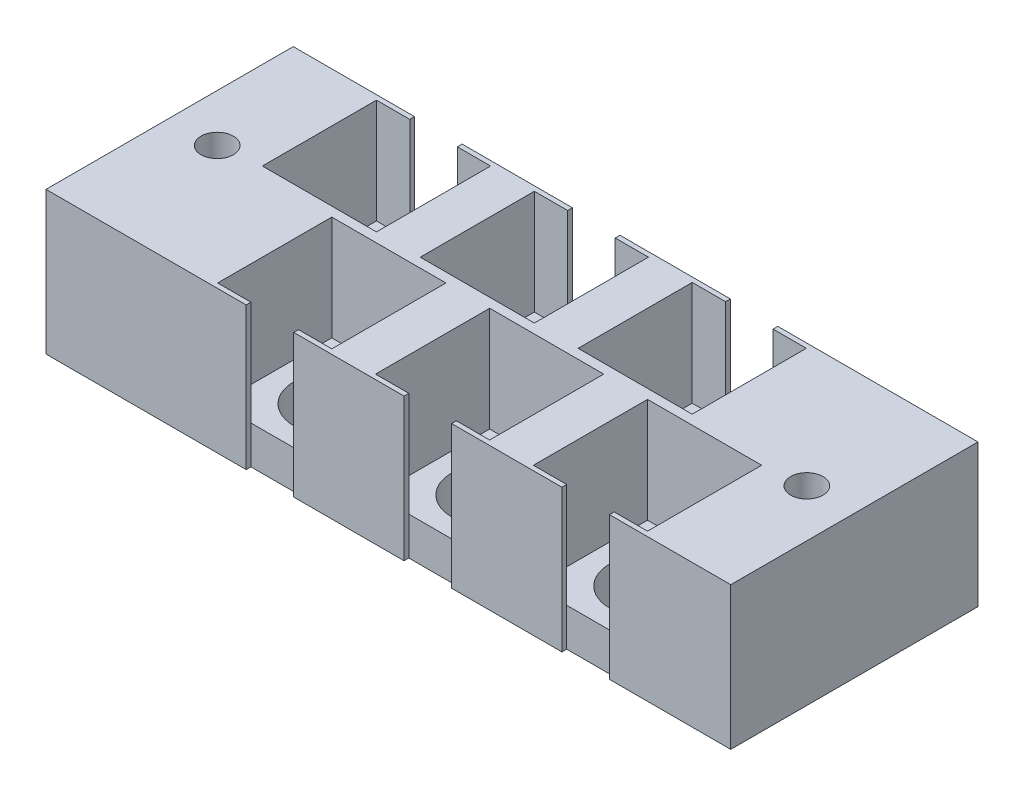
SolidWorks part; units mm, degrees
ref_plane "Front Plane" through (0, 0, 0) normal (0, 0, 1) x (1, 0, 0)
ref_plane "Top Plane" through (0, 0, 0) normal (0, 1, 0) x (1, 0, 0)
ref_plane "Right Plane" through (0, 0, 0) normal (1, 0, 0) x (0, 0, -1)
sketch "Sketch1" plane through (0, 0, 0) normal (0, 1, 0) x (1, 0, 0)
  line L0 (5.3864, -4.1649) -> (1.7864, -4.1649)
  line L1 (18.3864, -4.1649) -> (21.9864, -4.1649)
  line L2 (30.2864, -30.1649) -> (26.6864, -30.1649)
  line L3 (13.6864, -30.1649) -> (10.0864, -30.1649)
  line L4 (43.2864, -30.1649) -> (52.0364, -30.1649)
  line L5 (52.0364, -30.1649) -> (52.0364, -4.1649)
  line L6 (52.0364, -4.1649) -> (34.9864, -4.1649)
  line L7 (-11.2136, -4.1649) -> (-19.9636, -4.1649)
  line L8 (-19.9636, -4.1649) -> (-19.9636, -30.1649)
  line L9 (-19.9636, -30.1649) -> (-2.9136, -30.1649)
  line L10 (-14.9636, -4.1649) -> (-14.9636, -30.1649) construction
  line L11 (47.0364, -4.1649) -> (47.0364, -30.1649) construction
  circle A0 centre (-14.9636, -17.1649) radius 1.7
  circle A1 centre (47.0364, -17.1649) radius 1.7
  line B0 (34.9864, -17.1649) -> (34.9864, -4.1649)
  line B1 (10.0864, -30.1649) -> (6.0864, -30.1649)
  line B2 (-2.4136, -29.6649) -> (9.5864, -29.6649)
  line B3 (10.0864, -30.1649) -> (10.0864, -17.1649)
  line B4 (26.6864, -30.1649) -> (26.6864, -17.1649)
  line B5 (43.2864, -30.1649) -> (43.2864, -17.1649)
  line B6 (-2.9136, -17.1649) -> (-2.9136, -30.1649)
  line B7 (9.5864, -29.6649) -> (9.5864, -17.6649)
  line B8 (30.2864, -17.1649) -> (30.2864, -30.1649)
  line B9 (21.9864, -4.1649) -> (21.9864, -17.1649)
  line B10 (34.4864, -16.6649) -> (34.4864, -4.6649)
  line B11 (17.8864, -16.6649) -> (17.8864, -4.6649)
  line B12 (1.7864, -17.1649) -> (1.7864, -4.1649)
  line B13 (42.7864, -29.6649) -> (42.7864, -17.6649)
  line B14 (14.1864, -29.6649) -> (26.1864, -29.6649)
  line B15 (30.7864, -17.6649) -> (30.7864, -29.6649)
  line B16 (30.7864, -17.6649) -> (42.7864, -29.6649) construction
  line B17 (14.1864, -17.6649) -> (26.1864, -29.6649) construction
  line B18 (-2.4136, -17.6649) -> (9.5864, -29.6649) construction
  line B19 (43.2864, -17.1649) -> (30.2864, -17.1649)
  line B20 (1.2864, -16.6649) -> (1.2864, -4.6649)
  line B21 (14.1864, -17.6649) -> (14.1864, -29.6649)
  line B22 (26.6864, -30.1649) -> (22.6864, -30.1649)
  line B23 (30.2864, -30.1649) -> (34.2864, -30.1649)
  line B24 (43.2864, -30.1649) -> (39.2864, -30.1649)
  line B25 (-10.7136, -10.6649) -> (1.2864, -10.6649) construction
  line B26 (5.8864, -10.6649) -> (17.8864, -10.6649) construction
  line B27 (22.4864, -10.6649) -> (34.4864, -10.6649) construction
  line B28 (-2.4136, -23.6649) -> (9.5864, -23.6649) construction
  line B29 (14.1864, -23.6649) -> (26.1864, -23.6649) construction
  line B30 (30.7864, -23.6649) -> (42.7864, -23.6649) construction
  line B31 (-27.9152, -23.6649) -> (50.7342, -23.6649) construction
  line B32 (21.9864, -17.1649) -> (34.9864, -17.1649)
  line B33 (-27.9152, -10.6649) -> (50.7342, -10.6649) construction
  line B34 (28.4864, -16.6649) -> (28.4864, -4.6649) construction
  line B35 (36.7864, -17.6649) -> (36.7864, -29.6649) construction
  line B36 (20.1864, -17.6649) -> (20.1864, -29.6649) construction
  line B37 (11.8864, -16.6649) -> (11.8864, -4.6649) construction
  line B38 (3.5864, -17.6649) -> (3.5864, -29.6649) construction
  line B39 (-4.7136, -16.6649) -> (-4.7136, -4.6649) construction
  line B40 (22.4864, -4.6649) -> (22.4864, -16.6649)
  line B41 (22.4864, -16.6649) -> (34.4864, -16.6649)
  line B42 (34.4864, -4.6649) -> (22.4864, -4.6649)
  line B43 (34.4864, -16.6649) -> (22.4864, -4.6649) construction
  line B44 (34.4864, -4.6649) -> (22.4864, -16.6649) construction
  line B45 (34.9864, -4.1649) -> (30.9864, -4.1649)
  line B46 (21.9864, -4.1649) -> (25.9864, -4.1649)
  line B47 (30.9864, -4.1649) -> (30.9864, -4.6649)
  line B48 (25.9864, -4.1649) -> (25.9864, -4.6649)
  circle B49 centre (28.4864, -10.6649) radius 4
  line B50 (-2.4136, -17.6649) -> (-2.4136, -29.6649)
  line B51 (9.5864, -17.6649) -> (-2.4136, -17.6649)
  line B52 (-2.4136, -29.6649) -> (9.5864, -17.6649) construction
  line B53 (10.0864, -17.1649) -> (-2.9136, -17.1649)
  line B54 (-2.9136, -30.1649) -> (1.0864, -30.1649)
  line B55 (1.0864, -30.1649) -> (1.0864, -29.6649)
  line B56 (6.0864, -30.1649) -> (6.0864, -29.6649)
  circle B57 centre (3.5864, -23.6649) radius 4
  line B58 (26.1864, -29.6649) -> (26.1864, -17.6649)
  line B59 (26.1864, -17.6649) -> (14.1864, -17.6649)
  line B60 (14.1864, -29.6649) -> (26.1864, -17.6649) construction
  line B61 (26.6864, -17.1649) -> (13.6864, -17.1649)
  line B62 (13.6864, -17.1649) -> (13.6864, -30.1649)
  line B63 (13.6864, -30.1649) -> (17.6864, -30.1649)
  line B64 (17.6864, -30.1649) -> (17.6864, -29.6649)
  line B65 (22.6864, -30.1649) -> (22.6864, -29.6649)
  circle B66 centre (20.1864, -23.6649) radius 4
  line B67 (42.7864, -17.6649) -> (30.7864, -17.6649)
  line B68 (30.7864, -29.6649) -> (42.7864, -29.6649)
  line B69 (30.7864, -29.6649) -> (42.7864, -17.6649) construction
  line B70 (34.2864, -30.1649) -> (34.2864, -29.6649)
  line B71 (39.2864, -30.1649) -> (39.2864, -29.6649)
  circle B72 centre (36.7864, -23.6649) radius 4
  line B73 (5.8864, -4.6649) -> (5.8864, -16.6649)
  line B74 (5.8864, -16.6649) -> (17.8864, -16.6649)
  line B75 (17.8864, -4.6649) -> (5.8864, -4.6649)
  line B76 (17.8864, -16.6649) -> (5.8864, -4.6649) construction
  line B77 (17.8864, -4.6649) -> (5.8864, -16.6649) construction
  line B78 (5.3864, -17.1649) -> (18.3864, -17.1649)
  line B79 (18.3864, -17.1649) -> (18.3864, -4.1649)
  line B80 (5.3864, -4.1649) -> (5.3864, -17.1649)
  line B81 (18.3864, -4.1649) -> (14.3864, -4.1649)
  line B82 (5.3864, -4.1649) -> (9.3864, -4.1649)
  line B83 (14.3864, -4.1649) -> (14.3864, -4.6649)
  line B84 (9.3864, -4.1649) -> (9.3864, -4.6649)
  circle B85 centre (11.8864, -10.6649) radius 4
  line B86 (-10.7136, -4.6649) -> (-10.7136, -16.6649)
  line B87 (-10.7136, -16.6649) -> (1.2864, -16.6649)
  line B88 (1.2864, -4.6649) -> (-10.7136, -4.6649)
  line B89 (1.2864, -16.6649) -> (-10.7136, -4.6649) construction
  line B90 (1.2864, -4.6649) -> (-10.7136, -16.6649) construction
  line B91 (-11.2136, -17.1649) -> (1.7864, -17.1649)
  line B92 (-11.2136, -4.1649) -> (-11.2136, -17.1649)
  line B93 (1.7864, -4.1649) -> (-2.2136, -4.1649)
  line B94 (-11.2136, -4.1649) -> (-7.2136, -4.1649)
  line B95 (-2.2136, -4.1649) -> (-2.2136, -4.6649)
  line B96 (-7.2136, -4.1649) -> (-7.2136, -4.6649)
  circle B97 centre (-4.7136, -10.6649) radius 4
  dimension "D1" = 8.75
  dimension "D2" = 8.75
  dimension "D3" = 5
  dimension "D4" = 5
sketch_block_instance "Block1-5"
sketch_block "Block1" parameters "D3"=6, "D1"=12, "D2"=12, "D4"=12, "D5"=78.6494, "D6"=78.6494, "D7"=78.6494, "D8"=10.3235, "D9"=14.0261, "D10"=17.7654, "D11"=23.7534, "D12"=22.7743, "D13"=54.5
sketch_block_instance "Block2-2"
sketch_block "Block2" parameters "D1"=12
sketch_block_instance "Block2-3"
sketch_block_instance "Block2-4"
sketch_block_instance "Block2-5"
sketch_block_instance "Block2-6"
sketch_block_instance "Block2-7"
sketch_block_instance "Block3-1"
sketch_block "Block3"
sketch_block_instance "Block4-1"
sketch_block "Block4"
sketch_block_instance "Block5-1"
sketch_block "Block5"
sketch_block_instance "Block6-1"
sketch_block "Block6"
sketch_block_instance "Block7-1"
sketch_block "Block7"
sketch_block_instance "Block8-1"
sketch_block "Block8"
extrude "Boss-Extrude1" add sketch "Sketch1" along normal blind 4 contours B50 B2 B7 B51 B57 | B20 B88 B86 B87 B97 | B11 B75 B73 B74 B85 | B21 B14 B58 B59 B66 | B10 B42 B40 B41 B49 | B15 B68 B13 B67 B72 region at (11.8864, 0, 4.8346) region at (-0.4636, 0, 4.8346) region at (3.5864, 0, 29.4952) region at (15.9364, 0, 29.4952) region at (28.4864, 0, 4.8346) region at (32.5364, 0, 29.4952)
extrude "Boss-Extrude2" add sketch "Sketch1<3>" along normal blind 15 contours B92 L7 L8 L9 B6 B91 A0 | B5 L4 L5 L6 B0 B19 A1 | B78 B3 L3 B62 | B8 B32 B4 L2 | B12 B53 B80 L0 | B79 B61 B9 L1 | B56 B1 B3 B53 B6 B54 B55 B2 B50 B51 B7 | B65 B22 B4 B32 B61 B62 B63 B64 B14 B21 B59 B58 | B71 B24 B5 B19 B32 B8 B23 B70 B68 B15 B67 B13 | B48 B46 B9 B32 B0 B45 B47 B42 B10 B41 B40 | B84 B82 B80 B53 B78 B61 B79 B81 B83 B75 B11 B74 B73 | B96 B94 B92 B91 B53 B12 B93 B95 B88 B20 B87 B86 region at (3.5864, 0, 10.6649) region at (7.3864, 0, 4.3487) region at (1.6025, 0, 10.6649) region at (7.7364, 0, 17.3487) region at (11.8864, 0, 23.6649) region at (-12.7872, 0, 19.3141) region at (16.0364, 0, 17.3487) region at (20.1864, 0, 10.6649) region at (22.1702, 0, 10.6649) region at (28.4864, 0, 23.6649) region at (32.6364, 0, 17.3487) region at (44.8599, 0, 15.0156)
sketch "Sketch1<3>" plane through (0, 0, 0) normal (0, 1, 0) x (1, 0, 0) same geometry as "Sketch1"
sketch "Sketch2" plane through (0, 0, 0) normal (0, -1, 0) x (1, 0, 0)
  line L0 (-19.9636, 17.1649) -> (52.0364, 17.1649) construction
  line L3 (-0.4136, 30.1649) -> (-0.4136, 4.1649) construction
  line L6 (7.5864, 30.1649) -> (7.5864, 4.1649) construction
  line L7 (6.0864, 30.1649) -> (17.6864, 30.1649) construction
  line L8 (5.3864, 4.1649) -> (9.3864, 4.1649) construction
  line L10 (14.3864, 4.1649) -> (25.9864, 4.1649) construction
  line L11 (24.1864, 30.1649) -> (24.1864, 4.1649) construction
  line L12 (22.6864, 30.1649) -> (34.2864, 30.1649) construction
  line L13 (-19.9636, 30.1649) -> (1.0864, 30.1649) construction
  line L15 (1.7864, 4.1649) -> (-2.2136, 4.1649) construction
  line L16 (32.7864, 30.1649) -> (32.7864, 4.1649) construction
  line L17 (34.9864, 4.1649) -> (30.9864, 4.1649) construction
  point P2 (-41.2472, 26.0307)
  point P30 (-17.0515, 20.4955)
  line B0 (0.6864, 19.6649) -> (0.6864, 14.6649)
  line B1 (0.6864, 14.6649) -> (-1.5136, 14.6649)
  line B2 (-1.5136, 14.6649) -> (-1.5136, 19.6649)
  line B3 (-1.5136, 19.6649) -> (0.6864, 19.6649)
  line B4 (3.9864, 4.6649) -> (3.9864, 30.1649) construction
  line B5 (8.6864, 19.6649) -> (8.6864, 14.6649)
  line B6 (8.6864, 14.6649) -> (6.4864, 14.6649)
  line B7 (6.4864, 14.6649) -> (6.4864, 19.6649)
  line B8 (6.4864, 19.6649) -> (8.6864, 19.6649)
  line B9 (12.5864, 4.6649) -> (12.5864, 30.1649) construction
  line B10 (17.2864, 19.6649) -> (17.2864, 14.6649)
  line B11 (17.2864, 14.6649) -> (15.0864, 14.6649)
  line B12 (15.0864, 14.6649) -> (15.0864, 19.6649)
  line B13 (15.0864, 19.6649) -> (17.2864, 19.6649)
  line B14 (25.2864, 19.6649) -> (25.2864, 14.6649)
  line B15 (25.2864, 14.6649) -> (23.0864, 14.6649)
  line B16 (23.0864, 14.6649) -> (23.0864, 19.6649)
  line B17 (23.0864, 19.6649) -> (25.2864, 19.6649)
  line B18 (33.8864, 19.6649) -> (33.8864, 14.6649)
  line B19 (33.8864, 14.6649) -> (31.6864, 14.6649)
  line B20 (31.6864, 14.6649) -> (31.6864, 19.6649)
  line B21 (31.6864, 19.6649) -> (33.8864, 19.6649)
  dimension "D1" = 2.5
  dimension "D2" = 1.1
  dimension "D3" = 2.5
  dimension "D4" = 1.1
  dimension "D5" = 2.5
  dimension "D6" = 1.1
  dimension "D7" = 2.5
  dimension "D8" = 1.1
  dimension "D9" = 2.5
sketch_block_instance "Block9-4"
sketch_block "Block9"
sketch_block_instance "Block9-5"
sketch_block_instance "Block9-6"
sketch_block_instance "Block9-7"
sketch_block_instance "Block9-8"
extrude "Boss-Extrude3" add sketch "Sketch2" along normal blind 9
sketch "Sketch3" plane through (0, 0, 0) normal (0, -1, 0) x (1, 0, 0)
  text T0 "F8"
